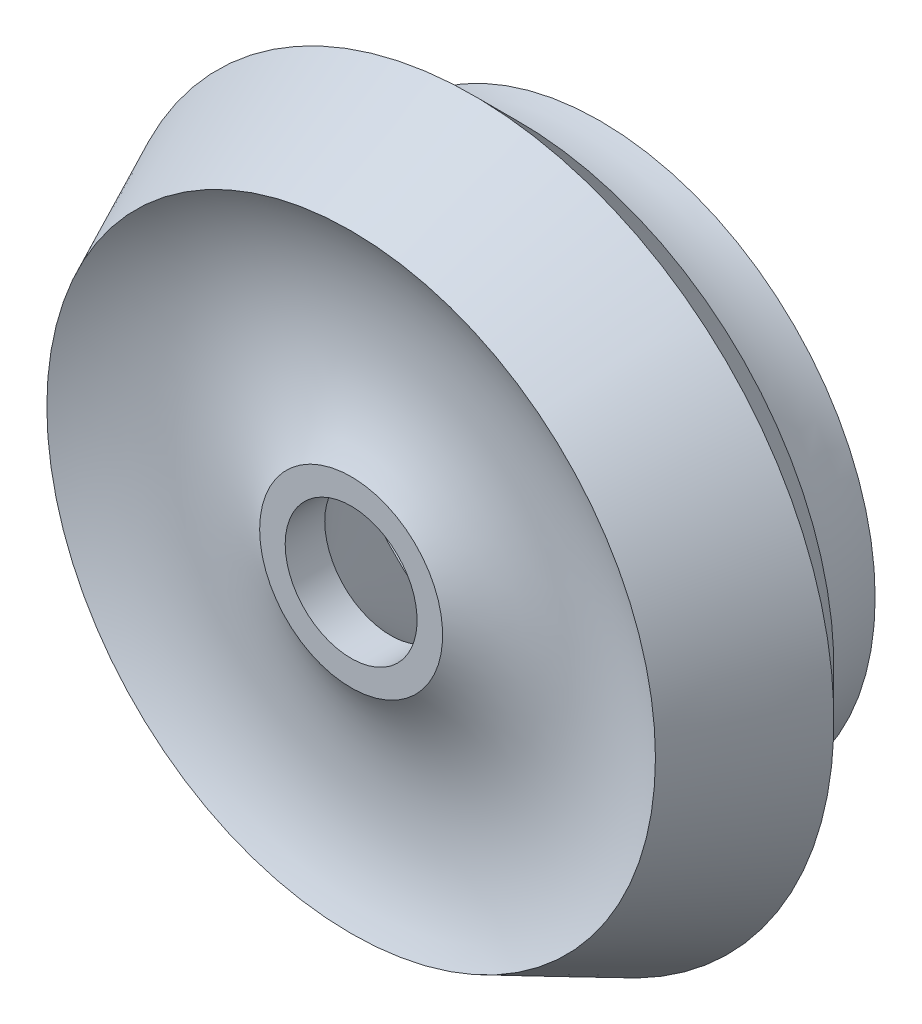
SolidWorks part; units mm, degrees
ref_plane "Front Plane" through (0, 0, 0) normal (0, 0, 1) x (1, 0, 0)
ref_plane "Top Plane" through (0, 0, 0) normal (0, 1, 0) x (1, 0, 0)
ref_plane "Right Plane" through (0, 0, 0) normal (1, 0, 0) x (0, 0, -1)
sketch "Hatch Sketch" plane through (0, 0, 0) normal (1, 0, 0) x (0, 0, -1)
  line L0 (-1132.4588, -713.8513) -> (-758.9546, -713.8513) construction
  line L1 (546.1, 0) -> (0, 0) construction
  line L2 (495, 230.6517) -> (495, 0) construction
  line L3 (495, 230.6517) -> (0, 0) construction
  line L4 (587.2743, 273.6481) -> (495, 230.6517)
  line L5 (475, 0) -> (735, 0) construction
  line L6 (525, 50) -> (475, 0) construction
  line L7 (525, 50) -> (495, 50)
  line L8 (525, 50) -> (658.8478, 183.8478)
  line L9 (495, 69.3483) -> (495, 50)
  line L10 (683.5965, 208.5965) -> (658.8478, 183.8478) construction
  line L11 (683.5965, 208.5965) -> (683.5965, 155.2015)
  line L12 (621.8227, 239.0997) -> (667.9612, 192.9612) construction
  line L13 (621.8227, 239.0997) -> (606.8256, 224.1027)
  line L14 (621.8227, 239.0997) -> (587.2743, 273.6481)
  arc A0 (546.1, 0) -> (495, 230.6517) centre (0, 0) ccw construction
  arc A1 (609.6, 0) -> (552.5581, 257.4717) centre (0, 0) ccw construction
  arc A2 (647.9, 0) -> (587.2743, 273.6481) centre (0, 0) ccw construction
  arc A3 (683.5965, 155.2015) -> (658.8478, 183.8478) centre (475, 0) ccw
  arc A4 (495, 69.3483) -> (495, 230.6517) centre (368.5275, 150) ccw
  arc A5 (735, 0) -> (540.171, 251.6997) centre (475, 0) ccw construction
  arc A6 (606.8256, 224.1027) -> (683.5965, 208.5965) centre (667.6682, 327.5347) ccw
  point P19 (546.1, 0)
  point P24 (475, 0)
  point P26 (683.5965, 155.2015)
  point P27 (683.5965, 208.5965)
  point P28 (607.7784, 224.4545)
  point P30 (607.7784, 224.4545)
  point P31 (0, 0)
  dimension "D5" = 260
  dimension "D1" = 546.1
  dimension "D3" = 609.6
  dimension "D4" = 647.9
  dimension "D8" = 150
  dimension "D11" = 120
  dimension "D2" = 495
  dimension "D7" = 475
  dimension "D6" = 45
  dimension "D9" = 30
  dimension "D10" = 35
revolve "Hatch Revolution" add sketch "Hatch Sketch" angle 360 about L1
